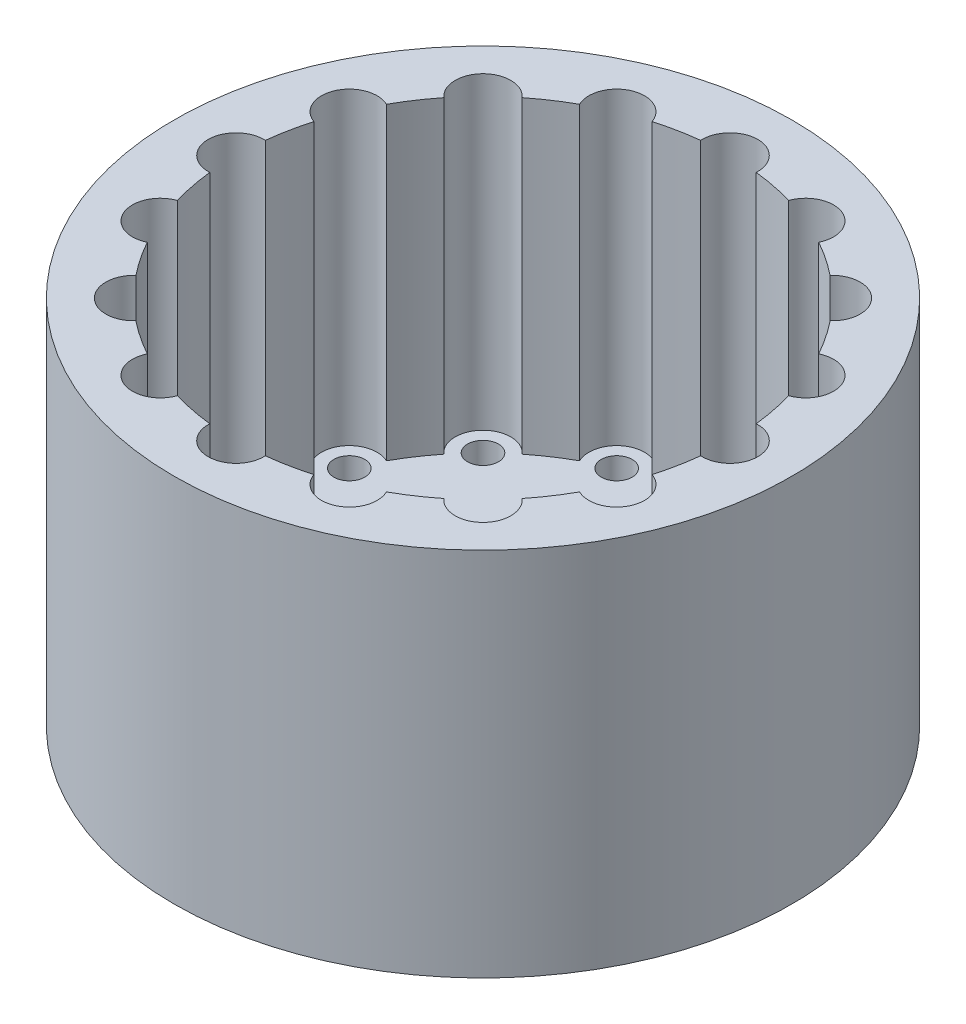
SolidWorks part; units mm, degrees
ref_plane "Front Plane" through (0, 0, 0) normal (0, 0, 1) x (1, 0, 0)
ref_plane "Top Plane" through (0, 0, 0) normal (0, 1, 0) x (1, 0, 0)
ref_plane "Right Plane" through (0, 0, 0) normal (1, 0, 0) x (0, 0, -1)
sketch "Sketch1" plane through (0, 0, 0) normal (0, 1, 0) x (1, 0, 0)
  arc A0 (-38.4407, 11.0596) -> (-39.7469, 4.4929) centre (0, 0) ccw
  arc A1 (4.4929, 39.7469) -> (-4.4929, 39.7469) centre (0, 40) ccw
  arc A2 (19.3613, 35.002) -> (11.0596, 38.4407) centre (15.3073, 36.9552) ccw
  arc A3 (31.2822, 24.9283) -> (24.9283, 31.2822) centre (28.2843, 28.2843) ccw
  arc A4 (38.4407, 11.0596) -> (35.002, 19.3613) centre (36.9552, 15.3073) ccw
  arc A5 (39.7469, -4.4929) -> (39.7469, 4.4929) centre (40, 0) ccw
  arc A6 (35.002, -19.3613) -> (38.4407, -11.0596) centre (36.9552, -15.3073) ccw
  arc A7 (24.9283, -31.2822) -> (31.2822, -24.9283) centre (28.2843, -28.2843) ccw
  arc A8 (11.0596, -38.4407) -> (19.3613, -35.002) centre (15.3073, -36.9552) ccw
  arc A9 (-4.4929, -39.7469) -> (4.4929, -39.7469) centre (0, -40) ccw
  arc A10 (-19.3613, -35.002) -> (-11.0596, -38.4407) centre (-15.3073, -36.9552) ccw
  arc A11 (-31.2822, -24.9283) -> (-24.9283, -31.2822) centre (-28.2843, -28.2843) ccw
  arc A12 (-38.4407, -11.0596) -> (-35.002, -19.3613) centre (-36.9552, -15.3073) ccw
  arc A13 (-39.7469, 4.4929) -> (-39.7469, -4.4929) centre (-40, 0) ccw
  arc A14 (-35.002, 19.3613) -> (-38.4407, 11.0596) centre (-36.9552, 15.3073) ccw
  arc A15 (-24.9283, 31.2822) -> (-31.2822, 24.9283) centre (-28.2843, 28.2843) ccw
  arc A16 (-11.0596, 38.4407) -> (-19.3613, 35.002) centre (-15.3073, 36.9552) ccw
  circle A17 centre (0, 0) radius 50
  arc A18 (-31.2822, 24.9283) -> (-35.002, 19.3613) centre (0, 0) ccw
  arc A19 (-19.3613, 35.002) -> (-24.9283, 31.2822) centre (0, 0) ccw
  arc A20 (-4.4929, 39.7469) -> (-11.0596, 38.4407) centre (0, 0) ccw
  arc A21 (11.0596, 38.4407) -> (4.4929, 39.7469) centre (0, 0) ccw
  arc A22 (24.9283, 31.2822) -> (19.3613, 35.002) centre (0, 0) ccw
  arc A23 (35.002, 19.3613) -> (31.2822, 24.9283) centre (0, 0) ccw
  arc A24 (39.7469, 4.4929) -> (38.4407, 11.0596) centre (0, 0) ccw
  arc A25 (38.4407, -11.0596) -> (39.7469, -4.4929) centre (0, 0) ccw
  arc A26 (31.2822, -24.9283) -> (35.002, -19.3613) centre (0, 0) ccw
  arc A27 (19.3613, -35.002) -> (24.9283, -31.2822) centre (0, 0) ccw
  arc A28 (-11.0596, -38.4407) -> (-4.4929, -39.7469) centre (0, 0) ccw
  arc A29 (-24.9283, -31.2822) -> (-19.3613, -35.002) centre (0, 0) ccw
  arc A30 (-35.002, -19.3613) -> (-31.2822, -24.9283) centre (0, 0) ccw
  arc A31 (-39.7469, -4.4929) -> (-38.4407, -11.0596) centre (0, 0) ccw
  arc A32 (4.4929, -39.7469) -> (11.0596, -38.4407) centre (0, 0) ccw
  point P2 (0, 0)
  point P3 (0, 0)
  point P31 (-107.6814, 18.7358)
  point P38 (0, 0)
  point P55 (0, 0)
  point P56 (0, 0)
  dimension "D1" = 16
  dimension "D2" = 100
extrude "Boss-Extrude1" add sketch "Sketch1" along normal blind 50
sketch "Sketch2" plane through (0, 0, 0) normal (0, -1, 0) x (1, 0, 0)
  circle A0 centre (0, 0) radius 50
extrude "Boss-Extrude2" add sketch "Sketch2" along normal blind 10
sketch "Sketch3" plane through (0, 0, 0) normal (0, 1, 0) x (1, 0, 0)
  circle A0 centre (0, 40) radius 2.5
  circle A1 centre (15.3073, 36.9552) radius 2.5
  circle A2 centre (28.2843, 28.2843) radius 2.5
  circle A3 centre (36.9552, 15.3073) radius 2.5
  circle A4 centre (40, 0) radius 2.5
  circle A5 centre (36.9552, -15.3073) radius 2.5
  circle A6 centre (28.2843, -28.2843) radius 2.5
  circle A7 centre (15.3073, -36.9552) radius 2.5
  circle A8 centre (0, -40) radius 2.5
  circle A9 centre (-15.3073, -36.9552) radius 2.5
  circle A10 centre (-28.2843, -28.2843) radius 2.5
  circle A11 centre (-36.9552, -15.3073) radius 2.5
  circle A12 centre (-40, 0) radius 2.5
  circle A13 centre (-36.9552, 15.3073) radius 2.5
  circle A14 centre (-28.2843, 28.2843) radius 2.5
  circle A15 centre (-15.3073, 36.9552) radius 2.5
  point P35 (0, 0)
  dimension "D1" = 5
  dimension "D2" = 16
extrude "Cut-Extrude1" cut sketch "Sketch3" against normal blind 4
